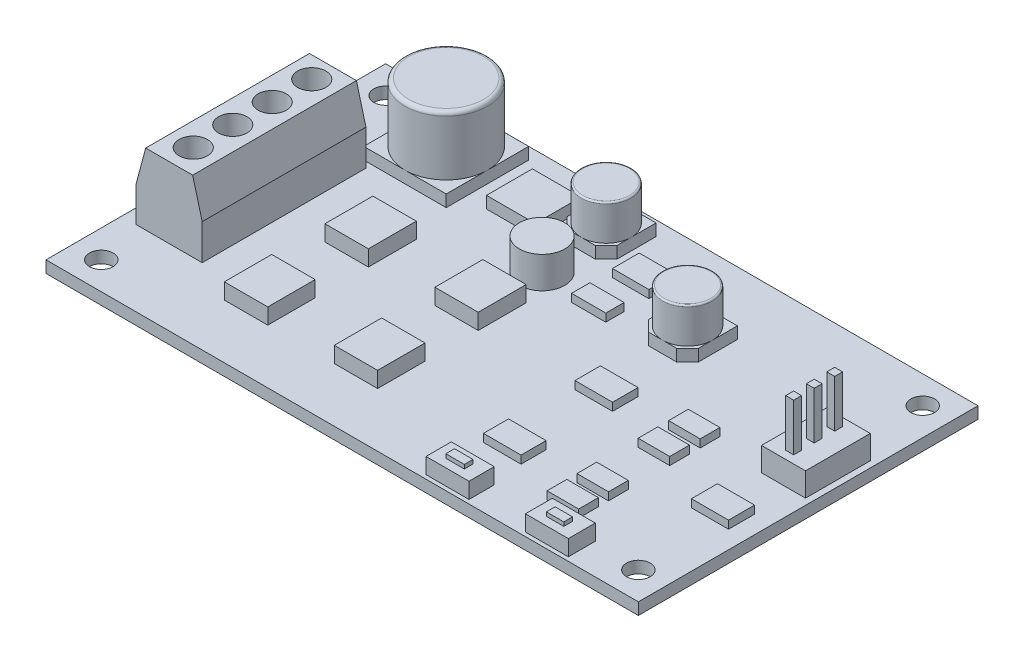
SolidWorks part; units mm, degrees
ref_plane "Front Plane" through (0, 0, 0) normal (0, 0, 1) x (1, 0, 0)
ref_plane "Top Plane" through (0, 0, 0) normal (0, 1, 0) x (1, 0, 0)
ref_plane "Right Plane" through (0, 0, 0) normal (1, 0, 0) x (0, 0, -1)
sketch "Sketch1" plane through (0, 0, 0) normal (0, 1, 0) x (1, 0, 0)
  line L0 (109.1076, 184.6821) -> (545.5379, 184.6821) construction
  line L2 (0, 0) -> (75, 0)
  line L3 (0, 0) -> (0, 43)
  line L4 (0, 43) -> (75, 43)
  line L5 (75, 0) -> (75, 43)
  dimension "D1" = 43
  dimension "D2" = 75
extrude "Boss-Extrude1" add sketch "Sketch1" along normal blind 1.5
sketch "Sketch2" plane through (0, 1.5, 0) normal (0, 1, 0) x (1, 0, 0)
  line L1 (0, 0) -> (0, 43) construction
  line L3 (0, 43) -> (75, 43) construction
  line L4 (0, 0) -> (75, 0) construction
  line L5 (75, 0) -> (75, 43) construction
  circle A0 centre (3.5, 39.5) radius 1.5
  circle A1 centre (71.5, 39.5) radius 1.5
  circle A2 centre (71.5, 3.5) radius 1.5
  circle A3 centre (3.5, 3.5) radius 1.5
  dimension "D1" = 3
  dimension "D2" = 3.5
  dimension "D3" = 3.5
  dimension "D4" = 3.5
  dimension "D5" = 3.5
extrude "Cut-Extrude3" cut sketch "Sketch2" against normal blind 1.5
sketch "Sketch3" plane through (0, 1.5, 0) normal (0, 1, 0) x (1, 0, 0)
  line L0 (9.1748, 32.8415) -> (10.9612, 31.0551)
  line L1 (9.1748, 31.0551) -> (19.617, 31.0551)
  line L2 (9.1748, 31.0551) -> (9.1748, 41.4974)
  line L3 (9.1748, 41.4974) -> (19.617, 41.4974)
  line L4 (19.617, 31.0551) -> (19.617, 41.4974)
  line L5 (9.1748, 31.0551) -> (19.617, 41.4974) construction
  line L6 (9.1748, 41.4974) -> (19.617, 31.0551) construction
  line L7 (17.8306, 31.0551) -> (19.617, 32.8415)
  circle A0 centre (14.3959, 36.2762) radius 5.2211
extrude "Boss-Extrude2" add sketch "Sketch3" along normal blind 1.5 separate body contours A0 L3 L2 | A0 | A0 L4 L3 | A0 L1 L7 L4 | L7 L1 L4 | L2 L1 L0 | A0 L2 L0 L1 region at (10.5551, 1.5, -32.4354) region at (9.7702, 1.5, -31.6506) region at (10.341, 1.5, -40.3311) region at (14.3959, 1.5, -36.2762) region at (18.2367, 1.5, -32.4354) region at (18.4508, 1.5, -40.3311) region at (19.0216, 1.5, -31.6506)
extrude "Boss-Extrude3" add sketch "Sketch3<3>" along normal blind 9 contours A0
sketch "Sketch3<3>" plane through (0, 1.5, 0) normal (0, 1, 0) x (1, 0, 0) same geometry as "Sketch3"
sketch "Sketch4" plane through (0, 1.5, 0) normal (0, 1, 0) x (1, 0, 0)
  line L1 (1.8491, 9.5693) -> (10.2047, 9.5693)
  line L2 (1.8491, 9.5693) -> (1.8491, 30.3035)
  line L3 (1.8491, 30.3035) -> (10.2047, 30.3035)
  line L4 (10.2047, 9.5693) -> (10.2047, 30.3035)
  line L5 (1.8491, 9.5693) -> (10.2047, 30.3035) construction
  line L6 (1.8491, 30.3035) -> (10.2047, 9.5693) construction
  point P0 (6.0269, 19.9364)
extrude "Boss-Extrude4" add sketch "Sketch4" along normal blind 9 separate body
chamfer "Chamfer1" distance 4.5 angle 15 2 edges at (10.2047, 10.5, -19.9364) (1.8491, 10.5, -19.9364) first distance on face at (10.2047, 6, -19.9364) first distance on face at (1.8491, 6, -19.9364)
sketch "Sketch6" plane through (0, 10.5, 0) normal (0, 1, 0) x (1, 0, 0)
  circle A0 centre (6.0218, 27.6224) radius 1.798
  dimension "D1" = 3.596
extrude "Cut-Extrude5" cut sketch "Sketch6" against normal blind 4.5
pattern_linear "LPattern1" count 4 spacing 5 along (0, 0, 1) of "Cut-Extrude5"
sketch "Sketch7" plane through (1.8491, 0, 0) normal (-1, 0, 0) x (0, 0, 1)
  line L0 (-27.6224, 3.75) -> (-27.6224, 9.951) construction
  line L1 (-28.8724, 2.5) -> (-26.3724, 2.5)
  line L2 (-28.8724, 2.5) -> (-28.8724, 5)
  line L3 (-28.8724, 5) -> (-26.3724, 5)
  line L4 (-26.3724, 2.5) -> (-26.3724, 5)
  line L5 (-28.8724, 2.5) -> (-26.3724, 5) construction
  line L6 (-28.8724, 5) -> (-26.3724, 2.5) construction
  line L7 (-29.4203, 10.5) -> (-29.4203, 6) construction
  line L8 (-25.8244, 6) -> (-25.8244, 10.5) construction
  line L17 (-30.3035, 1.5) -> (-9.5693, 1.5) construction
  point P0 (-27.6224, 3.75)
  dimension "D1" = 2.5
  dimension "D2" = 2.25
extrude "Cut-Extrude6" cut sketch "Sketch7" against normal blind 4.5
pattern_linear "LPattern2" count 4 spacing 5 along (0, 0, 1) of "Cut-Extrude6"
sketch "Sketch8" plane through (0, 1.5, 0) normal (0, 1, 0) x (1, 0, 0)
  line L1 (15.7017, 6.875) -> (21.2017, 6.875)
  line L2 (15.7017, 6.875) -> (15.7017, 12.875)
  line L3 (15.7017, 12.875) -> (21.2017, 12.875)
  line L4 (21.2017, 6.875) -> (21.2017, 12.875)
  line L5 (15.7017, 6.875) -> (21.2017, 12.875) construction
  line L6 (15.7017, 12.875) -> (21.2017, 6.875) construction
  line L7 (15.7017, 25.6827) -> (21.2017, 25.6827)
  line L8 (15.7017, 25.6827) -> (15.7017, 19.612)
  line L9 (15.7017, 19.612) -> (21.2017, 19.612)
  line L10 (21.2017, 25.6827) -> (21.2017, 19.612)
  line L11 (15.7017, 25.6827) -> (21.2017, 19.612) construction
  line L12 (15.7017, 19.612) -> (21.2017, 25.6827) construction
  line L13 (29.6224, 25.6827) -> (35.1079, 25.6827)
  line L14 (29.6224, 25.6827) -> (29.6224, 19.612)
  line L15 (29.6224, 19.612) -> (35.1079, 19.612)
  line L16 (35.1079, 25.6827) -> (35.1079, 19.612)
  line L17 (29.6224, 25.6827) -> (35.1079, 19.612) construction
  line L18 (29.6224, 19.612) -> (35.1079, 25.6827) construction
  line L19 (29.6224, 12.875) -> (35.1079, 12.875)
  line L20 (29.6224, 12.875) -> (29.6224, 6.875)
  line L21 (29.6224, 6.875) -> (35.1079, 6.875)
  line L22 (35.1079, 12.875) -> (35.1079, 6.875)
  line L23 (29.6224, 12.875) -> (35.1079, 6.875) construction
  line L24 (29.6224, 6.875) -> (35.1079, 12.875) construction
  point P0 (18.4517, 9.875)
  point P5 (32.3651, 22.6474)
  point P7 (18.4517, 22.6474)
  point P15 (32.3651, 9.875)
  dimension "D1" = 5.5
  dimension "D2" = 6
extrude "Boss-Extrude5" add sketch "Sketch8" along normal blind 2 separate body
sketch "Sketch9" plane through (0, 1.5, 0) normal (0, 1, 0) x (1, 0, 0)
  line L1 (22.3118, 39.2628) -> (28.4943, 39.2628)
  line L2 (22.3118, 39.2628) -> (22.3118, 33.4533)
  line L3 (22.3118, 33.4533) -> (28.4943, 33.4533)
  line L4 (28.4943, 39.2628) -> (28.4943, 33.4533)
  line L5 (22.3118, 39.2628) -> (28.4943, 33.4533) construction
  line L6 (22.3118, 33.4533) -> (28.4943, 39.2628) construction
  point P0 (25.403, 36.3581)
extrude "Boss-Extrude6" add sketch "Sketch9" along normal blind 1.5 separate body
sketch "Sketch10" plane through (0, 1.5, 0) normal (0, 1, 0) x (1, 0, 0)
  circle A0 centre (32.7753, 30.0331) radius 2.8758
extrude "Boss-Extrude7" add sketch "Sketch10" along normal blind 4 separate body
sketch "Sketch11" plane through (0, 1.5, 0) normal (0, 1, 0) x (1, 0, 0)
  line L0 (29.7597, 36.2109) -> (31.1239, 34.8466)
  line L1 (29.7597, 34.8466) -> (36.0739, 34.8466)
  line L2 (29.7597, 34.8466) -> (29.7597, 41.1609)
  line L3 (29.7597, 41.1609) -> (36.0739, 41.1609)
  line L4 (36.0739, 34.8466) -> (36.0739, 41.1609)
  line L5 (29.7597, 34.8466) -> (36.0739, 41.1609) construction
  line L6 (29.7597, 41.1609) -> (36.0739, 34.8466) construction
  line L7 (34.7097, 34.8466) -> (36.0739, 36.2109)
  line L8 (46.1914, 35.0311) -> (52.5057, 28.7168) construction
  line L9 (51.1415, 28.7168) -> (52.5057, 30.0811)
  line L10 (46.1914, 28.7168) -> (52.5057, 28.7168)
  line L11 (46.1914, 28.7168) -> (52.5057, 35.0311) construction
  line L12 (52.5057, 28.7168) -> (52.5057, 35.0311)
  line L13 (46.1914, 28.7168) -> (46.1914, 35.0311)
  line L14 (46.1914, 35.0311) -> (52.5057, 35.0311)
  line L15 (46.1914, 30.0811) -> (47.5557, 28.7168)
  circle A0 centre (32.9168, 38.0037) radius 3.1571
  circle A1 centre (49.3486, 31.874) radius 3.1571
  point P0 (32.9168, 38.0037)
  point P11 (49.3486, 31.874)
extrude "Boss-Extrude8" add sketch "Sketch11" along normal up to vertex (1.5 mm away) separate body contours A0 L3 L2 | A0 | A0 L4 L3 | A0 L1 L7 L4 | A0 L2 L0 L1 | A1 L14 L13 | A1 | A1 L12 L14 | A1 L10 L9 L12 | A1 L13 L15 L10 region at (30.6577, 1.5, -35.7447) region at (30.4649, 1.5, -40.4557) region at (32.9168, 1.5, -38.0037) region at (35.1759, 1.5, -35.7447) region at (35.3687, 1.5, -40.4557) region at (51.6077, 1.5, -29.6149) region at (47.0895, 1.5, -29.6149) region at (49.3486, 1.5, -31.874) region at (51.8005, 1.5, -34.3259) region at (46.8967, 1.5, -34.3259) up to point (19.617, 3, -31.0551)
extrude "Boss-Extrude9" add sketch "Sketch11<3>" along normal blind 6 contours A0 | A1
sketch "Sketch11<3>" plane through (0, 1.5, 0) normal (0, 1, 0) x (1, 0, 0) same geometry as "Sketch11"
sketch "Sketch12" plane through (0, 1.5, 0) normal (0, 1, 0) x (1, 0, 0)
  line L1 (47.7211, 22.4729) -> (52.4795, 22.4729)
  line L2 (47.7211, 22.4729) -> (47.7211, 19.2495)
  line L3 (47.7211, 19.2495) -> (52.4795, 19.2495)
  line L4 (52.4795, 22.4729) -> (52.4795, 19.2495)
  line L5 (47.7211, 22.4729) -> (52.4795, 19.2495) construction
  line L6 (47.7211, 19.2495) -> (52.4795, 22.4729) construction
  line L7 (47.7211, 10.8375) -> (52.4795, 10.8375)
  line L8 (47.7211, 10.8375) -> (47.7211, 7.6652)
  line L9 (47.7211, 7.6652) -> (52.4795, 7.6652)
  line L10 (52.4795, 10.8375) -> (52.4795, 7.6652)
  line L11 (47.7211, 10.8375) -> (52.4795, 7.6652) construction
  line L12 (47.7211, 7.6652) -> (52.4795, 10.8375) construction
  line L13 (37.8069, 37.3012) -> (42.4203, 37.3012)
  line L14 (37.8069, 37.3012) -> (37.8069, 33.9057)
  line L15 (37.8069, 33.9057) -> (42.4203, 33.9057)
  line L16 (42.4203, 37.3012) -> (42.4203, 33.9057)
  line L17 (37.8069, 37.3012) -> (42.4203, 33.9057) construction
  line L18 (37.8069, 33.9057) -> (42.4203, 37.3012) construction
  line L19 (68.0528, 16.9654) -> (72.7478, 16.9654)
  line L20 (68.0528, 16.9654) -> (68.0528, 13.6662)
  line L21 (68.0528, 13.6662) -> (72.7478, 13.6662)
  line L22 (72.7478, 16.9654) -> (72.7478, 13.6662)
  line L23 (68.0528, 16.9654) -> (72.7478, 13.6662) construction
  line L24 (68.0528, 13.6662) -> (72.7478, 16.9654) construction
  point P0 (50.1003, 20.8612)
  point P5 (50.1003, 9.2513)
  point P10 (40.1136, 35.6034)
  point P15 (70.4003, 15.3158)
extrude "Boss-Extrude10" add sketch "Sketch12" along normal blind 1 separate body
sketch "Sketch13" plane through (0, 1.5, 0) normal (0, 1, 0) x (1, 0, 0)
  line L1 (58.0437, 7.8954) -> (62.0437, 7.8954)
  line L2 (58.0437, 7.8954) -> (58.0437, 5.3954)
  line L3 (58.0437, 5.3954) -> (62.0437, 5.3954)
  line L4 (62.0437, 7.8954) -> (62.0437, 5.3954)
  line L5 (58.0437, 7.8954) -> (62.0437, 5.3954) construction
  line L6 (58.0437, 5.3954) -> (62.0437, 7.8954) construction
  line L7 (58.0437, 11.6772) -> (62.0437, 11.6772)
  line L8 (58.0437, 11.6772) -> (58.0437, 9.1772)
  line L9 (58.0437, 9.1772) -> (62.0437, 9.1772)
  line L10 (62.0437, 11.6772) -> (62.0437, 9.1772)
  line L11 (58.0437, 11.6772) -> (62.0437, 9.1772) construction
  line L12 (58.0437, 9.1772) -> (62.0437, 11.6772) construction
  line L13 (58.0437, 19.4245) -> (62.0437, 19.4245)
  line L14 (58.0437, 19.4245) -> (58.0437, 16.9245)
  line L15 (58.0437, 16.9245) -> (62.0437, 16.9245)
  line L16 (62.0437, 19.4245) -> (62.0437, 16.9245)
  line L17 (58.0437, 19.4245) -> (62.0437, 16.9245) construction
  line L18 (58.0437, 16.9245) -> (62.0437, 19.4245) construction
  line L19 (58.0437, 23.2798) -> (62.0437, 23.2798)
  line L20 (58.0437, 23.2798) -> (58.0437, 20.7798)
  line L21 (58.0437, 20.7798) -> (62.0437, 20.7798)
  line L22 (62.0437, 23.2798) -> (62.0437, 20.7798)
  line L23 (58.0437, 23.2798) -> (62.0437, 20.7798) construction
  line L24 (58.0437, 20.7798) -> (62.0437, 23.2798) construction
  line L25 (37.9432, 30.9202) -> (42.2758, 30.9202)
  line L26 (37.9432, 30.9202) -> (37.9432, 28.5992)
  line L27 (37.9432, 28.5992) -> (42.2758, 28.5992)
  line L28 (42.2758, 30.9202) -> (42.2758, 28.5992)
  line L29 (37.9432, 30.9202) -> (42.2758, 28.5992) construction
  line L30 (37.9432, 28.5992) -> (42.2758, 30.9202) construction
  point P0 (60.0437, 6.6454)
  point P5 (60.0437, 10.4272)
  point P10 (60.0437, 18.1745)
  point P15 (60.0437, 22.0298)
  point P25 (40.1095, 29.7597)
  dimension "D1" = 2.5
  dimension "D2" = 4
extrude "Boss-Extrude11" add sketch "Sketch13" along normal blind 1 separate body
sketch "Sketch14" plane through (0, 1.5, 0) normal (0, 1, 0) x (1, 0, 0)
  line L1 (47.6157, 3.6985) -> (53.0521, 3.6985)
  line L2 (47.6157, 3.6985) -> (47.6157, 0.5007)
  line L3 (47.6157, 0.5007) -> (53.0521, 0.5007)
  line L4 (53.0521, 3.6985) -> (53.0521, 0.5007)
  line L5 (47.6157, 3.6985) -> (53.0521, 0.5007) construction
  line L6 (47.6157, 0.5007) -> (53.0521, 3.6985) construction
  line L7 (60.194, 3.9117) -> (65.6304, 3.9117)
  line L8 (60.194, 3.9117) -> (60.194, 0.5007)
  line L9 (60.194, 0.5007) -> (65.6304, 0.5007)
  line L10 (65.6304, 3.9117) -> (65.6304, 0.5007)
  line L11 (60.194, 3.9117) -> (65.6304, 0.5007) construction
  line L12 (60.194, 0.5007) -> (65.6304, 3.9117) construction
  point P0 (50.3339, 2.0996)
  point P5 (62.9122, 2.2062)
extrude "Boss-Extrude12" add sketch "Sketch14" along normal blind 2 separate body
sketch "Sketch15" plane through (0, 3.5, 0) normal (0, 1, 0) x (1, 0, 0)
  line L1 (49.0693, 2.648) -> (51.4192, 2.648)
  line L2 (49.0693, 2.648) -> (49.0693, 1.5465)
  line L3 (49.0693, 1.5465) -> (51.4192, 1.5465)
  line L4 (51.4192, 2.648) -> (51.4192, 1.5465)
  line L5 (49.0693, 2.648) -> (51.4192, 1.5465) construction
  line L6 (49.0693, 1.5465) -> (51.4192, 2.648) construction
  line L7 (61.8101, 2.648) -> (64.0131, 2.648)
  line L8 (61.8101, 2.648) -> (61.8101, 1.5465)
  line L9 (61.8101, 1.5465) -> (64.0131, 1.5465)
  line L10 (64.0131, 2.648) -> (64.0131, 1.5465)
  line L11 (61.8101, 2.648) -> (64.0131, 1.5465) construction
  line L12 (61.8101, 1.5465) -> (64.0131, 2.648) construction
  point P0 (50.2442, 2.0973)
  point P5 (62.9116, 2.0973)
extrude "Boss-Extrude13" add sketch "Sketch15" along normal blind 0.5
sketch "Sketch16" plane through (0, 1.5, 0) normal (0, 1, 0) x (1, 0, 0)
  line L1 (68.6443, 21.9427) -> (74.2147, 21.9427)
  line L2 (68.6443, 21.9427) -> (68.6443, 30.1435)
  line L3 (68.6443, 30.1435) -> (74.2147, 30.1435)
  line L4 (74.2147, 21.9427) -> (74.2147, 30.1435)
  line L5 (68.6443, 21.9427) -> (74.2147, 30.1435) construction
  line L6 (68.6443, 30.1435) -> (74.2147, 21.9427) construction
  point P0 (71.4295, 26.0431)
extrude "Boss-Extrude14" add sketch "Sketch16" along normal blind 3 separate body
sketch "Sketch17" plane through (0, 4.5, 0) normal (0, 1, 0) x (1, 0, 0)
  line L0 (74.2147, 21.9427) -> (74.2147, 30.1435) construction
  line L1 (70.7147, 28.1435) -> (71.7147, 28.1435)
  line L2 (70.7147, 28.1435) -> (70.7147, 29.1435)
  line L3 (70.7147, 29.1435) -> (71.7147, 29.1435)
  line L4 (71.7147, 28.1435) -> (71.7147, 29.1435)
  line L5 (70.7147, 28.1435) -> (71.7147, 29.1435) construction
  line L6 (70.7147, 29.1435) -> (71.7147, 28.1435) construction
  line L7 (74.2147, 30.1435) -> (68.6443, 30.1435) construction
  point P0 (71.2147, 28.6435)
  dimension "D1" = 1
  dimension "D2" = 3
  dimension "D3" = 1.5
extrude "Boss-Extrude15" add sketch "Sketch17" along normal blind 6
pattern_linear "LPattern3" count 3 spacing 2.6 along (0, 0, 1) of "Boss-Extrude15"
chamfer "Chamfer2" distance 0.5 angle 60 16 edges at (1.8491, 2.5, -12.6224) (1.8491, 3.75, -11.3724) (1.8491, 5, -12.6224) (1.8491, 3.75, -13.8724) (1.8491, 3.75, -16.3724) (1.8491, 2.5, -17.6224) (1.8491, 5, -17.6224) (1.8491, 3.75, -18.8724) (1.8491, 2.5, -22.6224) (1.8491, 3.75, -21.3724) (1.8491, 5, -22.6224) (1.8491, 3.75, -23.8724) (1.8491, 3.75, -26.3724) (1.8491, 2.5, -27.6224) (1.8491, 5, -27.6224) (1.8491, 3.75, -28.8724) tangent propagation no first distance on face at (1.8491, 3.75, -17.6224)
fillet "Fillet1" radius 0.5 1 edges at (14.3959, 10.5, -31.0551)
fillet "Fillet2" radius 0.2 1 edges at (32.9168, 7.5, -34.8466)
fillet "Fillet3" radius 0.2 1 edges at (49.3486, 7.5, -28.7168)
